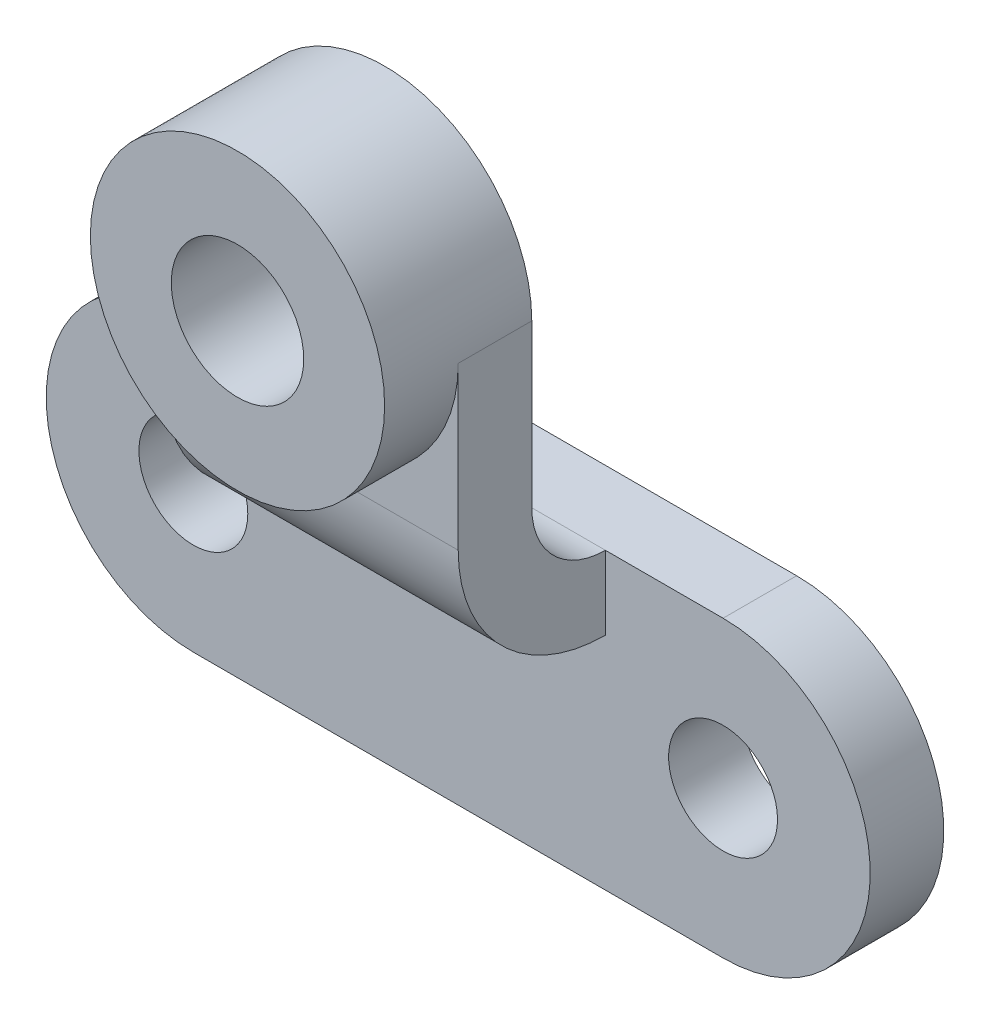
SolidWorks part; units mm, degrees
ref_plane "Front Plane" through (0, 0, 0) normal (0, 0, 1) x (1, 0, 0)
ref_plane "Top Plane" through (0, 0, 0) normal (0, 1, 0) x (1, 0, 0)
ref_plane "Right Plane" through (0, 0, 0) normal (1, 0, 0) x (0, 0, -1)
sketch "Sketch1" plane through (0, 0, 0) normal (0, 0, 1) x (1, 0, 0)
  line L0 (-90, 0) -> (90, 0) construction
  line L1 (-90, 50) -> (90, 50)
  line L2 (-90, -50) -> (90, -50)
  line L3 (0, -55) -> (0, 55) construction
  line L4 (0, 0) -> (0, 130) construction
  arc A0 (-90, 50) -> (-90, -50) centre (-90, 0) ccw
  arc A1 (90, -50) -> (90, 50) centre (90, 0) ccw
  circle A2 centre (-90, 0) radius 18.5
  circle A3 centre (90, 0) radius 18.5
  circle A4 centre (0, 130) radius 22.5
  circle A5 centre (0, 130) radius 50
  point P3 (0, 0)
  dimension "D2" = 50
  dimension "D3" = 37
  dimension "D4" = 45
  dimension "D5" = 100
  dimension "D1" = 180
  dimension "D6" = 130
extrude "Boss-Extrude1" add sketch "Sketch1" along normal blind 25 contours L2 A1 L1 A0 A2 A3 region at (0, 0, 0)
extrude "Boss-Extrude2" add sketch "Sketch1<3>" against normal blind 50 from offset 100 separate body contours A5 A4 region at (-48.5858, 130, 0)
sketch "Sketch1<3>" plane through (0, 0, 0) normal (0, 0, 1) x (1, 0, 0) same geometry as "Sketch1"
sketch "Sketch2" plane through (0, 0, 0) normal (1, 0, 0) x (0, 0, -1)
  line L4 (-12.5, 50) -> (-50, 50) construction
  line L5 (-25, 50) -> (0, 50) construction
  line L6 (-50, 50) -> (-50, 130) construction
  line L7 (-50, 80) -> (-50, 180) construction
  line L8 (-50, 130) -> (-50, 75)
  line L9 (-25, 50) -> (-12.5, 50)
  line L10 (-25, 25) -> (-12.5, 25)
  line L11 (-75, 130) -> (-75, 75)
  line L12 (-75, 130) -> (-50, 130)
  line L13 (-12.5, 25) -> (-12.5, 50)
  arc A0 (-25, 50) -> (-50, 75) centre (-25, 75) cw
  arc A1 (-25, 25) -> (-75, 75) centre (-25, 75) cw
  dimension "D1" = 25
  dimension "D2" = 25
extrude "Boss-Extrude3" add sketch "Sketch2" along normal mid plane 100
sketch "Sketch3" plane through (0, 0, 75) normal (0, 0, 1) x (1, 0, 0)
  line L0 (22.5, 130) -> (-22.5, 130) construction
  line L1 (22.5, 130) -> (-22.5, 130)
  arc A0 (-22.5, 130) -> (22.5, 130) centre (0, 130) ccw construction
  arc A1 (-22.5, 130) -> (22.5, 130) centre (0, 130) ccw
extrude "Cut-Extrude1" cut sketch "Sketch3" against normal through all
